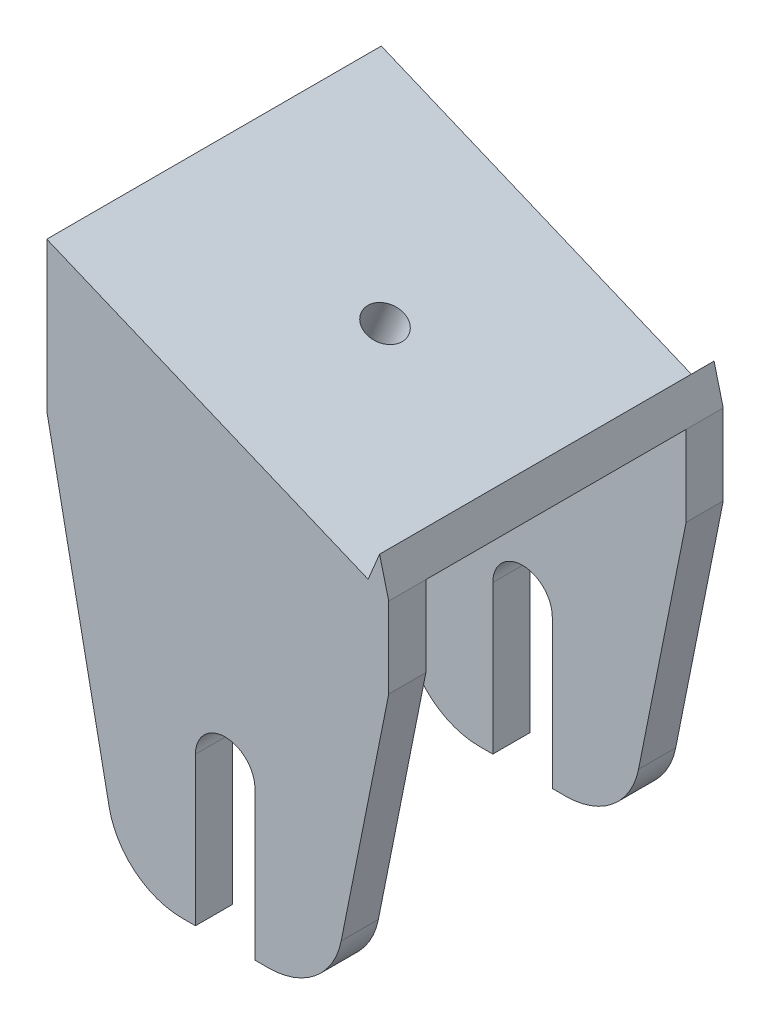
SolidWorks part; units mm, degrees
ref_plane "Alzado" through (0, 0, 0) normal (0, 0, 1) x (1, 0, 0)
ref_plane "Planta" through (0, 0, 0) normal (0, 1, 0) x (1, 0, 0)
ref_plane "Vista lateral" through (0, 0, 0) normal (1, 0, 0) x (0, 0, -1)
sketch "Croquis1" plane through (0, 0, 0) normal (0, 0, 1) x (1, 0, 0)
  line L1 (5.1699, 17.4529) -> (-42.8301, 37.4529)
  line L5 (-14.8301, -12.5471) -> (-14.8301, -32.5471)
  line L6 (-22.8301, -12.5471) -> (-22.8301, -32.5471)
  line L7 (-14.8301, -32.5471) -> (-13.0282, -32.5471)
  line L8 (-22.8301, -32.5471) -> (-24.6321, -32.5471)
  line L9 (-3.2224, -24.5082) -> (5.1699, 17.4529)
  line L10 (-34.4379, -24.5082) -> (-42.8301, 17.4529)
  line L11 (-42.8301, 37.4529) -> (-42.8301, 17.4529)
  arc A0 (-14.8301, -12.5471) -> (-22.8301, -12.5471) centre (-18.8301, -12.5471) ccw
  arc A1 (-34.4379, -24.5082) -> (-24.6321, -32.5471) centre (-24.6321, -22.5471) ccw
  arc A2 (-3.2224, -24.5082) -> (-13.0282, -32.5471) centre (-13.0282, -22.5471) cw
  dimension "D1" = 10
  dimension "D2" = 20
extrude "Saliente-Extruir1" add sketch "Croquis1" along normal blind 45
sketch "Croquis2" plane through (-22.8301, 0, 0) normal (1, 0, 0) x (0, 0, -1)
  line L0 (-40, -32.5471) -> (-5, -32.5471)
  line L1 (-45, -32.5471) -> (0, -32.5471) construction
  line L2 (-40, -32.5471) -> (-40, 11.743)
  line L3 (-5, 11.743) -> (-5, 27.4529)
  line L4 (-5, 11.743) -> (-5, -32.5471)
  line L5 (-5, 27.4529) -> (-40, 27.3828)
  line L8 (-40, 27.3828) -> (-40, 11.743)
extrude "Cortar-Extruir1" cut sketch "Croquis2" against normal blind 25 and the other way blind 35
sketch "Croquis3" plane through (6.9611, 16.7066, 0) normal (0.3846, 0.9231, 0) x (0.9231, -0.3846, 0)
  line L0 (-53.9405, -45) -> (-53.9405, 0)
  line L1 (-53.9405, 0) -> (-1.9405, 0)
  line L2 (-1.9405, 0) -> (5.7404, 0)
  line L3 (-1.9405, -45) -> (-53.9405, -45)
  line L4 (5.7404, 0) -> (5.7404, -45)
  line L5 (5.7404, -45) -> (-1.9405, -45)
extrude "Saliente-Extruir2" add sketch "Croquis3" along normal blind 0.0001 and the other way blind 10
sketch "Croquis4" plane through (0, 0, 45) normal (0, 0, 1) x (1, 0, 0)
  line L0 (-42.8301, 17.4529) -> (-42.8301, 41.6595)
  line L1 (3.1699, 7.4529) -> (3.1699, 41.6595)
  line L2 (3.1699, 41.6595) -> (-42.8301, 41.6595)
  line L3 (-42.8301, 17.4529) -> (-56.321, 17.4529)
  line L4 (-56.321, 17.4529) -> (-56.321, 53.4787)
  line L5 (-56.321, 53.4787) -> (16.2461, 53.4787)
  line L6 (16.2461, 53.4787) -> (17.1357, 1.881)
  line L7 (3.1699, 7.4529) -> (4.9112, 4.9346)
  line L8 (4.9112, 4.9346) -> (17.1357, 1.881)
extrude "Cortar-Extruir2" cut sketch "Croquis4" against normal blind 50.0001
sketch "Croquis5" plane through (6.9611, 16.7067, 0) normal (0.3846, 0.9231, 0) x (0.9231, -0.3846, 0)
  circle A0 centre (-29.0238, -22.5) radius 2.5
extrude "Cortar-Extruir3" cut sketch "Croquis5" against normal blind 20 contours A0
sketch "Croquis6" plane through (3.1699, 0, 0) normal (1, 0, 0) x (0, 0, -1)
  line L0 (-40, 7.4529) -> (-40, 12.4529)
  line L1 (-40, 7.4529) -> (-5, 7.4529)
  line L2 (-5, 7.4529) -> (-5, 12.4529)
  line L3 (-5, 12.4529) -> (-40, 12.4529)
extrude "Cortar-Extruir4" cut sketch "Croquis6" against normal blind 50
fillet "Redondeo7" radius 10 1 edges at (3.1699, 12.4529, 22.5)
sketch "Croquis7" plane through (0, 0, 45) normal (0, 0, 1) x (1, 0, 0)
  line L0 (0.4006, 19.4402) -> (1.9391, 23.1325)
  line L1 (-42.8301, 37.453) -> (3.1699, 18.2864) construction
  line L3 (1.9391, 23.1325) -> (3.1699, 18.2864)
  line L4 (3.1699, 18.2864) -> (0.4006, 19.4402)
extrude "Saliente-Extruir3" add sketch "Croquis7" against normal up to vertex (45 mm away) up to point (3.1699, 18.2864, 0)
